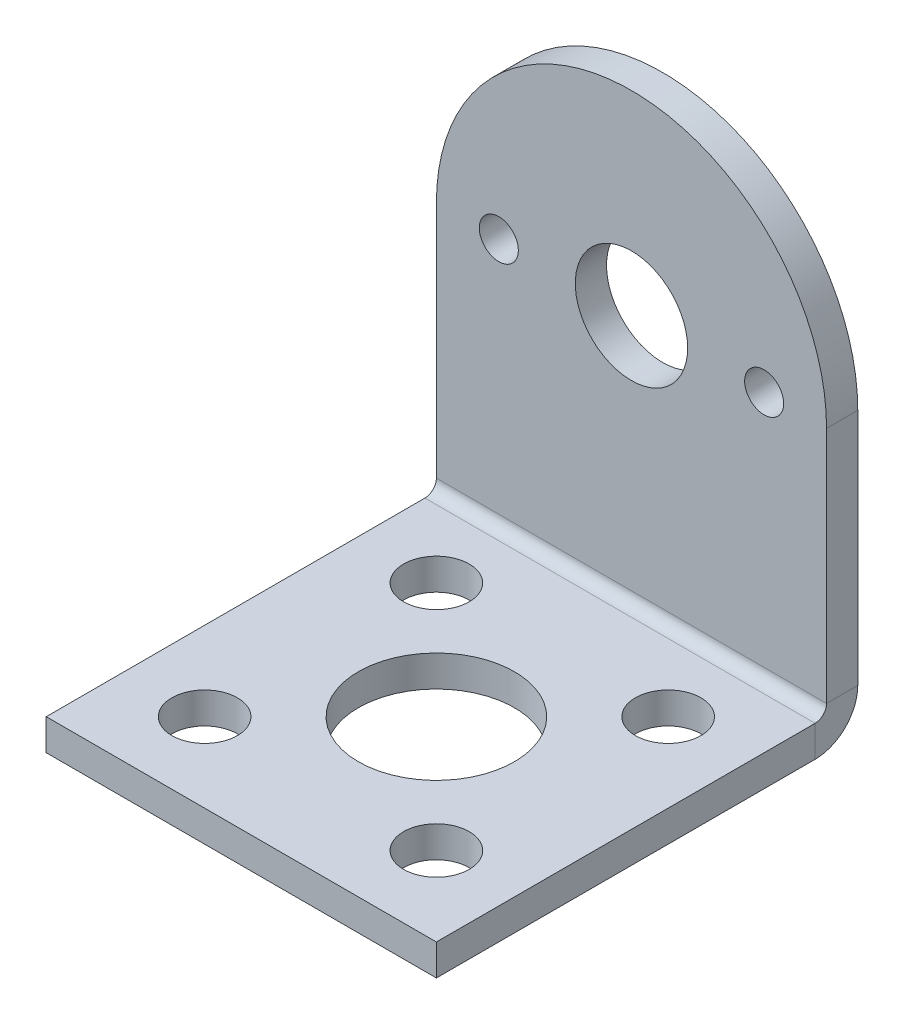
SolidWorks part; units mm, degrees
note: The reader was unsure of these and kept them because the rebuilt part matched: flange length of "边线-法兰1".
ref_plane "前视基准面" through (0, 0, 0) normal (0, 0, 1) x (1, 0, 0)
ref_plane "上视基准面" through (0, 0, 0) normal (0, 1, 0) x (1, 0, 0)
ref_plane "右视基准面" through (0, 0, 0) normal (1, 0, 0) x (0, 0, -1)
sketch "草图1" plane through (0, 0, 0) normal (0, 0, 1) x (1, 0, 0)
  line L0 (12.5, 0) -> (-12.5, 0)
  line L1 (-12.5, 0) -> (-12.5, 18)
  line L2 (0, 0) -> (0, 34.5142) construction
  line L3 (12.5, 0) -> (12.5, 18)
  line L4 (-12.5, 18) -> (12.5, 18) construction
  arc A0 (-12.5, 18) -> (12.5, 18) centre (0, 18) cw
  circle A1 centre (0, 18) radius 3.6
  circle A2 centre (-8.5, 18) radius 1.25
  circle A3 centre (8.5, 18) radius 1.25
  dimension "D1" = 25
  dimension "D3" = 7.2
  dimension "D4" = 2.5
  dimension "D2" = 18
  dimension "D5" = 17
base flange "基体-法兰1" sketch "草图1" thickness 2 reverse thickness direction no parameters "D1"=0.7366
edge flange "边线-法兰1" sketch "草图10" flange angle 90 flange length 27 bend radius 0.7366 thickness 2 relief rectangular parameters "D6"=10
sketch "草图10" plane through (0, 0, 0) normal (0, -1, 0) x (1, 0, 0)
  line L0 (-12.5, 0) -> (12.5, 0) construction
  line L1 (-12.5, 0) -> (12.5, 0)
  line L2 (-12.5, 0) -> (-12.5, 25)
  line L3 (-12.5, 25) -> (12.5, 25)
  line L4 (12.5, 25) -> (12.5, 0)
  line L5 (0, 25) -> (0, 12.5) construction
  line L6 (0, 12.5) -> (-12.5, 12.5) construction
  circle A0 centre (0, 12.5) radius 5
  circle A1 centre (-7.425, 5.075) radius 2.1
  circle A2 centre (-7.425, 19.925) radius 2.1
  circle A3 centre (7.425, 5.075) radius 2.1
  circle A4 centre (7.425, 19.925) radius 2.1
  point P13 (2.7724, -2)
  dimension "D1" = 10
  dimension "D2" = 4.2
  dimension "D3" = 14.85
  dimension "D4" = 14.85
  dimension "D5" = 25
bend "边线折弯1" bend radius 0.7366 bend angle 90 parameters "D5"=1
sketch "折弯-线1" plane through (0, 0, 0) normal (0, 1, 0) x (1, 0, 0)
sketch "边界框1" plane through (0, 0, 0) normal (0, 1, 0) x (1, 0, 0)
sheet metal parameters "钣金6" thickness 2 parameters "D1"=0.7366
flat pattern "平板型式6" [suppressed]
sketch "折弯-线2" plane through (0, 0, 0) normal (0, 1, 0) x (1, 0, 0)
sketch "边界框2" [suppressed] plane through (0, 0, 0) normal (0, 1, 0) x (1, 0, 0)
sheet metal parameters "钣金7" thickness 2 parameters "D1"=0.7366
flat pattern "平板型式6" [suppressed]
sketch "折弯-线2" plane through (0, 0, 0) normal (0, 1, 0) x (1, 0, 0)
sketch "边界框2" [suppressed] plane through (0, 0, 0) normal (0, 1, 0) x (1, 0, 0)
bend of the flat pattern "展平-<边线折弯1>1"
